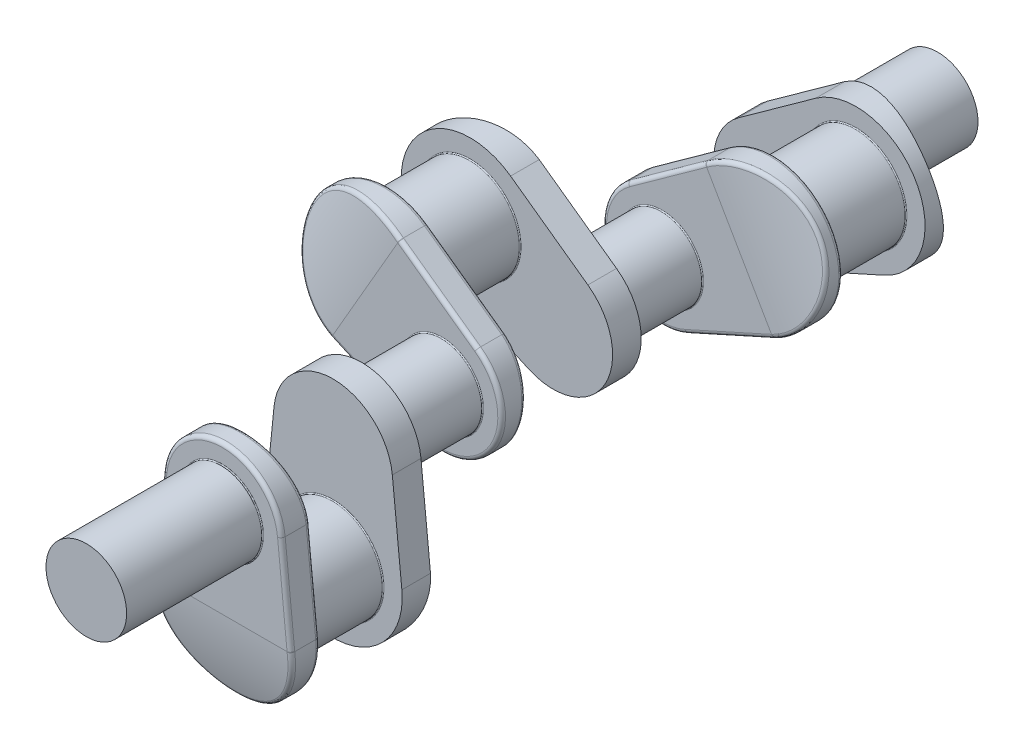
SolidWorks part; units mm, degrees
ref_plane "Front Plane" through (0, 0, 0) normal (0, 0, 1) x (1, 0, 0)
ref_plane "Top Plane" through (0, 0, 0) normal (0, 1, 0) x (1, 0, 0)
ref_plane "Right Plane" through (0, 0, 0) normal (1, 0, 0) x (0, 0, -1)
sketch "Sketch1" plane through (0, 0, 0) normal (0, 0, 1) x (1, 0, 0)
  circle A0 centre (0, 0) radius 33.1
  dimension "D1" = 66.2
extrude "Boss-Extrude1" add sketch "Sketch1" along normal blind 27.31
sketch "Sketch2" plane through (0, 0, 27.31) normal (0, 0, 1) x (1, 0, 0)
  line L0 (-39.2523, 67.445) -> (-45.5704, 4.58)
  line L1 (39.2523, 67.445) -> (45.5704, 4.58)
  arc A0 (-45.5704, 4.58) -> (45.5704, 4.58) centre (0, 0) ccw
  circle A2 centre (0, 0) radius 33.1 construction
  arc A3 (39.2523, 67.445) -> (-39.2523, 67.445) centre (0, 63.5) ccw
  dimension "D1" = 12.7
  dimension "D2" = 63.5
extrude "Boss-Extrude2" add sketch "Sketch2" along normal blind 19
sketch "Sketch3" plane through (0, 0, 46.31) normal (0, 0, 1) x (1, 0, 0)
  circle A0 centre (0, 63.5) radius 26.75
  dimension "D1" = 53.5
extrude "Boss-Extrude3" add sketch "Sketch3" along normal blind 26.67 contours A0
sketch "Sketch4" plane through (0, 0, 0) normal (1, 0, 0) x (0, 0, -1)
  line L0 (-46.31, -45.8) -> (-27.31, -45.8) construction
  line L1 (-46.31, 4.58) -> (-69.1204, 4.58)
  line L2 (-69.1204, 4.58) -> (-69.1204, -45.8)
  line L3 (-69.1204, -45.8) -> (-36.81, -45.8)
  arc A0 (-46.31, 4.58) -> (-36.81, -45.8) centre (122.5917, 10.3436) ccw
  dimension "D1" = 169
extrude "Cut-Extrude1" cut sketch "Sketch4" against normal mid plane 156.72 contours L3 A0 L1 L2
sketch "Sketch5" plane through (0, 0, 0) normal (1, 0, 0) x (0, 0, -1)
  line L0 (-27.31, 102.95) -> (-46.31, 102.95) construction
  line L1 (-27.31, 67.445) -> (-27.31, 102.95) construction
  line L2 (-32.31, 102.95) -> (-13.3458, 102.95)
  line L3 (-13.3458, 102.95) -> (-13.3458, 67.445)
  line L4 (-13.3458, 67.445) -> (-27.31, 67.445)
  arc A0 (-32.31, 102.95) -> (-27.31, 67.445) centre (-196.2145, 61.7636) cw
  dimension "D2" = 169
  dimension "D1" = 5
extrude "Cut-Extrude2" cut sketch "Sketch5" against normal mid plane 156.72
fillet "Fillet1" radius 2.54 8 edges at (42.4113, 36.0125, 46.31) (-42.4113, 36.0125, 46.31) (0, 102.95, 46.31) (-42.4113, 36.0125, 27.31) (42.4113, 36.0125, 27.31) (0, -45.8, 27.31) (0.2049, -45.7995, 36.8102) (4.9235, 102.6416, 32.2328)
fillet "Fillet2" radius 0.64 2 edges at (33.1, 0, 27.31) (26.75, 63.5, 46.31)
mirror "Mirror2" about plane through (0, 0, 0) normal (0, 0, 1) of "Boss-Extrude1", "Boss-Extrude3", "Cut-Extrude1", "Boss-Extrude2", "Fillet2"
pattern_linear "LPattern1" count 3 spacing 145.96 along (0, 0, -1) of bodies 106
ref_axis "Axis1" through (0, 63.5, 164.7872) along (0, 0, -1)
move or copy body "Body-Move/Copy1" bodies to move or copy 107 copy no rotation origin (0, 63.5, 0) rotation axis (0, 0, -1) rotation angle 120
move or copy body "Body-Move/Copy2" bodies to move or copy 108 copy no rotation origin (0, 63.5, 0) rotation axis (0, 0, 1) rotation angle 120
combine bodies "Combine4" operation type add bodies to combine 106 109 110
sketch "Sketch6" plane through (0, 0, 72.98) normal (0, 0, 1) x (1, 0, 0)
  circle A1 centre (0, 63.5) radius 26.75
  circle A2 centre (0, 63.5) radius 26.75
  dimension "D1" = 0
extrude "Boss-Extrude4" add sketch "Sketch6" along normal blind 63.5
sketch "Sketch7" plane through (0, 0, -364.9) normal (0, 0, -1) x (-1, 0, 0)
  circle A1 centre (0, 63.5) radius 26.75
  circle A2 centre (0, 63.5) radius 26.75
  dimension "D1" = 0
extrude "Boss-Extrude5" add sketch "Sketch7" along normal blind 63.5 contours A2
